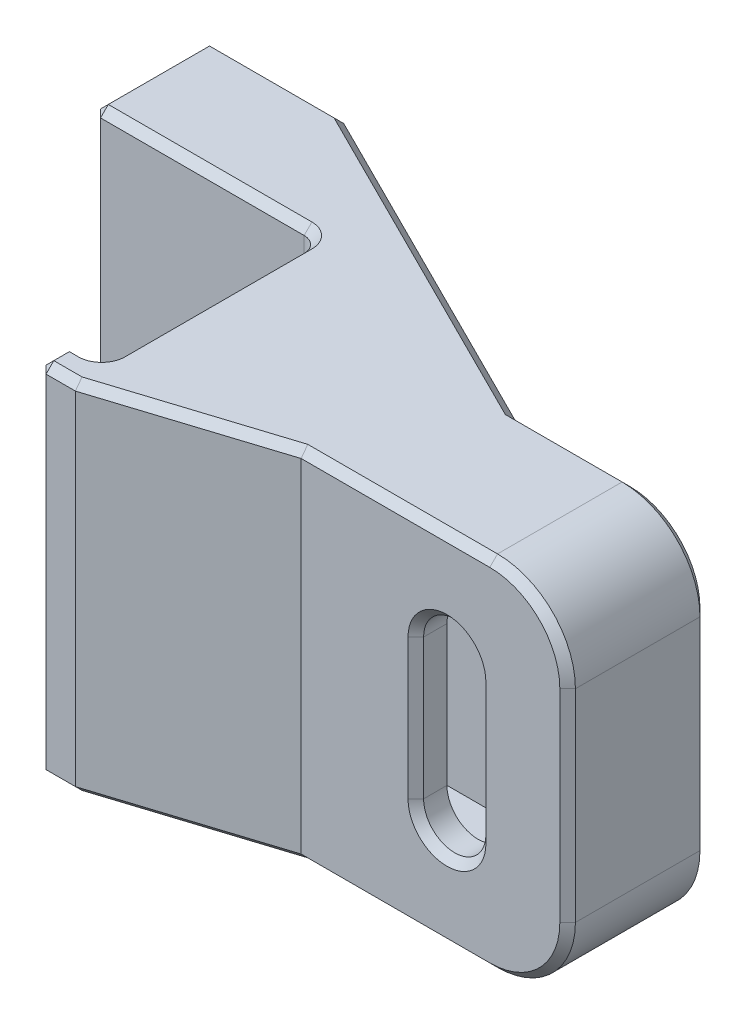
SolidWorks part; units mm, degrees
material "PET"
ref_plane "Front Plane" through (0, 0, 0) normal (0, 0, 1) x (1, 0, 0)
ref_plane "Top Plane" through (0, 0, 0) normal (0, 1, 0) x (1, 0, 0)
ref_plane "Right Plane" through (0, 0, 0) normal (1, 0, 0) x (0, 0, -1)
sketch "Reference" plane through (0, 0, 0) normal (0, 1, 0) x (1, 0, 0)
  line L0 (0, 0) -> (4, 0) construction
  line L1 (4, 0) -> (26, 7) construction
  line L2 (26, 7) -> (56, 7) construction
  line L3 (56, 7) -> (56, 15) construction
  line L4 (56, 15) -> (26, 15) construction
  line L5 (26, 15) -> (4, 26) construction
  line L6 (4, 26) -> (0, 26) construction
  point P8 (0, 0)
  point P10 (30, 15)
  point P11 (4, 19.1439)
  point P12 (0, 26)
  dimension "D1" = 4
  dimension "D2" = 26
  dimension "D3" = 30
  dimension "D4" = 8
  dimension "D5" = 15
  dimension "D6" = 11
sketch "Sketch2" plane through (0, 0, 0) normal (0, 1, 0) x (1, 0, 0)
  line L0 (61, 20) -> (26.2361, 20) construction
  line L1 (36.2361, 20) -> (-7.7639, 42)
  line L2 (-25, 42) -> (-25, 27)
  line L44 (0, -5) -> (4.7763, -5)
  line L45 (4.7763, -5) -> (26.7763, 2)
  line L46 (26.7763, 2) -> (61, 2)
  line L47 (61, 2) -> (61, 20)
  line L48 (61, 20) -> (36.2361, 20)
  line L49 (0, -5) -> (0, -1)
  line L50 (-25, 42) -> (-7.7639, 42)
  line L51 (4.2361, 27) -> (0, 27)
  line L52 (26.2361, 16) -> (4.2361, 27)
  line L53 (57, 16) -> (26.2361, 16)
  line L54 (57, 6) -> (57, 16)
  line L55 (26.1553, 6) -> (57, 6)
  line L56 (4.1553, -1) -> (26.1553, 6)
  line L57 (0, -1) -> (4.1553, -1)
  line L58 (4.2361, 27) -> (-25, 27)
  line L59 (26.2361, 16) -> (4.2361, 27)
  line L60 (57, 16) -> (26.2361, 16)
  line L61 (57, 6) -> (57, 16)
  line L62 (26.1553, 6) -> (57, 6)
  line L63 (4.1553, -1) -> (26.1553, 6)
  line L64 (0, -1) -> (4.1553, -1)
  point P8 (-12.5666, 27)
  dimension "D3" = 12
  dimension "D4" = 25
  dimension "D5" = 15
  dimension "D1" = 1
  dimension "D2" = 4
extrude "Create internal geometry" add sketch "Sketch2" along normal blind 38
sketch "Sketch4" plane through (0, 0, -2) normal (0, 0, 1) x (1, 0, 0)
  line L0 (45.5, 28) -> (45.5, 10) construction
  line L1 (49.5, 28) -> (49.5, 10)
  line L2 (41.5, 28) -> (41.5, 10)
  line L3 (61, 19) -> (-25, 19) construction
  line L4 (61, 38) -> (61, 0) construction
  line L5 (-25, 38) -> (-25, 0) construction
  line L6 (61, 38) -> (61, 0) construction
  arc A0 (49.5, 28) -> (41.5, 28) centre (45.5, 28) ccw
  arc A1 (41.5, 10) -> (49.5, 10) centre (45.5, 10) ccw
  point P2 (45.5, 19)
  point P13 (0, 0)
  dimension "D1" = 8
  dimension "D2" = 18
  dimension "D3" = 11.5
extrude "Cut shackle hole" cut sketch "Sketch4" against normal through all
ref_plane "Mid plane" through (0, 19, 0) normal (0, 1, 0) x (1, 0, 0)
sketch "Sketch3" plane through (0, 38, 0) normal (0, 1, 0) x (1, 0, 0)
  line L0 (-25, 27) -> (4.2361, 27) construction
  line L1 (-25, 42) -> (-25, 27) construction
  line L2 (-7.7639, 42) -> (-25, 42) construction
  line L3 (36.2361, 20) -> (-7.7639, 42) construction
  line L4 (61, 20) -> (36.2361, 20) construction
  line L5 (61, 2) -> (61, 20) construction
  line L6 (26.7763, 2) -> (61, 2) construction
  line L7 (4.7763, -5) -> (26.7763, 2) construction
  line L8 (0, -5) -> (4.7763, -5) construction
  line L9 (4.1553, -1) -> (0, -1) construction
  line L10 (0, -1) -> (0, -5) construction
  line L11 (-25, 27) -> (2.1553, 27)
  line L12 (-25, 42) -> (-25, 27)
  line L13 (-7.7639, 42) -> (-25, 42)
  line L14 (36.2361, 20) -> (-7.7639, 42)
  line L15 (61, 20) -> (36.2361, 20)
  line L16 (61, 2) -> (61, 20)
  line L17 (26.7763, 2) -> (61, 2)
  line L18 (4.7763, -5) -> (26.7763, 2)
  line L19 (0, -5) -> (4.7763, -5)
  line L20 (2.1553, -1) -> (0, -1)
  line L21 (0, -1) -> (0, -5)
  line L22 (4.1553, 25) -> (4.1553, 1)
  arc A0 (4.1553, 1) -> (2.1553, -1) centre (2.1553, 1) cw
  arc A1 (4.1553, 25) -> (2.1553, 27) centre (2.1553, 25) ccw
  dimension "D1" = 2
extrude "Cap top end" add sketch "Sketch3" along normal blind 4
mirror "Mirror top cap to bottom" about plane through (0, 19, 0) normal (0, 1, 0) of "Cap top end"
fillet "Round corners" radius 10 4 edges at (61, 42, -11) (61, -4, -11) (57, 38, -11) (57, 0, -11)
chamfer "Unnecessary chamfers" distance 1 angle 45 44 edges at (61, 19, -2) (61, 19, -20) (58.0711, -1.0711, -20) (58.0711, -1.0711, -2) (58.0711, 39.0711, -2) (58.0711, 39.0711, -20) (43.618, -4, -20) (14.2361, -4, -31) (-16.382, -4, -42) (-25, -4, -34.5) (-11.4224, -4, -27) (3.5695, -4, -26.4142) (4.1553, -4, -13) (3.5695, -4, 0.4142) (1.0776, -4, 1) (0, -4, 3) (38.8881, -4, -2) (15.7763, -4, 1.5) (2.3881, -4, 5) (38.8881, 42, -2) (15.7763, 42, 1.5) (2.3881, 42, 5) (0, 19, 5) (0, 42, 3) (0, 19, 1) (1.0776, 42, 1) (3.5695, 42, 0.4142) (4.1553, 42, -13) (3.5695, 42, -26.4142) (-11.4224, 42, -27) (-25, 19, -27) (-25, 42, -34.5) (43.618, 42, -20) (14.2361, 42, -31) (-16.382, 42, -42) (-25, 19, -42) (49.5, 19, -20) (45.5, 32, -20) (45.5, 6, -20) (41.5, 19, -20) (45.5, 32, -2) (41.5, 19, -2) (49.5, 19, -2) (45.5, 6, -2)
